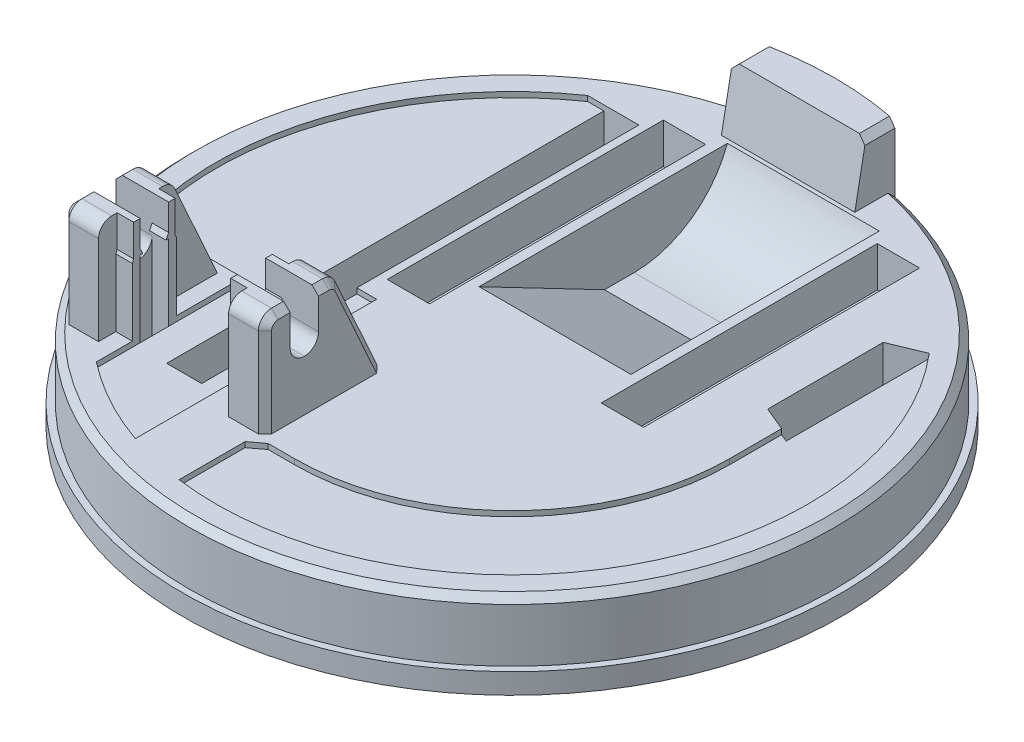
SolidWorks part; units mm, degrees
ref_plane "Front Plane" through (0, 0, 0) normal (0, 0, 1) x (1, 0, 0)
ref_plane "Top Plane" through (0, 0, 0) normal (0, 1, 0) x (1, 0, 0)
ref_plane "Right Plane" through (0, 0, 0) normal (1, 0, 0) x (0, 0, -1)
sketch "Sketch1" plane through (0, 0, 0) normal (0, 1, 0) x (1, 0, 0)
  circle A0 centre (0, 0) radius 49.9
  dimension "D1" = 99.8
extrude "Boss-Extrude1" add sketch "Sketch1" along normal blind 3.1
sketch "Sketch2" plane through (0, 0, 0) normal (0, -1, 0) x (1, 0, 0)
  circle A0 centre (0, 0) radius 48.9
  dimension "D1" = 97.8
extrude "Boss-Extrude2" add sketch "Sketch2" against normal blind 12.2
sketch "Sketch3" plane through (0, 12.2, 0) normal (0, 1, 0) x (1, 0, 0)
  line L0 (0, -48.9) -> (0, 41.8)
  line L2 (-10.1, 49.3) -> (10.1, 49.3)
  line L3 (-10.1, 49.3) -> (-10.1, 41.8)
  line L4 (-10.1, 41.8) -> (10.1, 41.8)
  line L5 (10.1, 49.3) -> (10.1, 41.8)
  circle A0 centre (0, 0) radius 48.9 construction
  circle A1 centre (0, 0) radius 48.9 construction
  point P12 (0, 41.8)
  circle M6 centre (0, 0) radius 48.9
  dimension "D1" = 90.7
  dimension "D2" = 7.5
  dimension "D3" = 20.2
extrude "Boss-Extrude3" add sketch "Sketch3" along normal blind 9 contours L5 L2 L3 L4 M6
sketch "Sketch4" plane through (10.1, 0, 0) normal (1, 0, 0) x (0, 0, -1)
  line L0 (41.8, 12.2) -> (43.5, 21.2)
  line L1 (47.8456, 21.2) -> (41.8, 21.2) construction
  line L2 (41.8, 21.2) -> (41.8, 12.2)
  line L3 (41.8, 21.2) -> (43.5, 21.2)
  dimension "D1" = 5.4
extrude "Cut-Extrude1" cut sketch "Sketch4" against normal up to surface (20.2 mm away) up to face at (-10.1, 16.7, -44.8228)
sketch "Sketch5" plane through (0, 12.2, 0) normal (0, 1, 0) x (1, 0, 0)
  line L0 (-10.1, 47.8456) -> (-10.1, 41.8) construction
  line L1 (-8.6, 41.2) -> (14.4, 41.2)
  line L2 (-8.6, 41.2) -> (-8.6, 3.6)
  line L3 (-8.6, 3.6) -> (14.4, 3.6)
  line L4 (14.4, 41.2) -> (14.4, 3.6)
  line L5 (-10.1, 41.8) -> (10.1, 41.8) construction
  dimension "D1" = 1.5
  dimension "D2" = 37.6
  dimension "D3" = 23
  dimension "D4" = 0.6
extrude "Cut-Extrude2" cut sketch "Sketch5" against normal blind 9.9
fillet "Fillet1" radius 15 1 edges at (2.9, 2.3, -41.2)
chamfer "Chamfer2" distance 9.9 distance2 19 1 edges at (2.9, 2.3, -3.6)
sketch "Sketch6" plane through (0, 12.2, 0) normal (0, 1, 0) x (1, 0, 0)
  line L0 (-8.6, 41.2) -> (-8.6, 3.6) construction
  line L1 (-16.5, 39.4) -> (-10.1, 39.4)
  line L2 (-16.5, 39.4) -> (-16.5, -2.4)
  line L3 (-16.5, -2.4) -> (-10.1, -2.4)
  line L4 (-10.1, 39.4) -> (-10.1, -2.4)
  line L5 (-8.6, 3.6) -> (14.4, 3.6) construction
  line L6 (-13.3, 35.1) -> (21.253, 35.1) construction
  line L7 (-16.5, 18.5) -> (-10.1, 18.5) construction
  line L8 (2.9, 41.2) -> (2.9, 3.6) construction
  line L9 (14.4, 41.2) -> (-8.6, 41.2) construction
  line L10 (22.3, -2.4) -> (15.9, -2.4)
  line L11 (15.9, 39.4) -> (15.9, -2.4)
  line L12 (22.3, 39.4) -> (15.9, 39.4)
  line L13 (22.3, 39.4) -> (22.3, -2.4)
  circle A0 centre (-13.3, 32.9) radius 2.2
  circle A1 centre (-13.3, 4.1) radius 2.2
  circle A2 centre (19.1, 4.1) radius 2.2
  circle A3 centre (19.1, 32.9) radius 2.2
  dimension "D6" = 4.4
  dimension "D1" = 1.5
  dimension "D2" = 41.8
  dimension "D3" = 6
  dimension "D4" = 6.4
  dimension "D5" = 3.2
  dimension "D7" = 4.3
extrude "Cut-Extrude3" cut sketch "Sketch6" against normal blind 6.1
sketch "Sketch7" plane through (0, 12.2, 0) normal (0, 1, 0) x (1, 0, 0)
  circle A0 centre (-13.3, 4.1) radius 2.2
  circle A1 centre (-13.3, 32.9) radius 2.2
  circle A2 centre (19.1, 32.9) radius 2.2
  circle A3 centre (19.1, 4.1) radius 2.2
  dimension "D1" = 4.4
  dimension "D2" = 4.4
  dimension "D3" = 4.4
  dimension "D4" = 4.4
extrude "Cut-Extrude4" cut sketch "Sketch7" against normal through all both and the other way through all
sketch "Sketch9" plane through (0, 12.2, 0) normal (0, 1, 0) x (1, 0, 0)
  line L0 (-16.5, 39.4) -> (-16.5, -2.4) construction
  line L1 (-23, 36.9) -> (-17.7, 36.9)
  line L2 (-23, 36.9) -> (-23, -29.3)
  line L3 (-23, -29.3) -> (-17.7, -29.3)
  line L4 (-17.7, 36.9) -> (-17.7, -29.3)
  line L5 (-10.1, 39.4) -> (-16.5, 39.4) construction
  dimension "D1" = 1.2
  dimension "D2" = 2.5
  dimension "D3" = 66.2
  dimension "D4" = 5.3
extrude "Cut-Extrude5" cut sketch "Sketch9" against normal through all both
sketch "Sketch12" plane through (0, 12.2, 0) normal (0, 1, 0) x (1, 0, 0)
  line L1 (-35.7, -14.4174) -> (-30.2, -14.4174)
  line L2 (-35.7, -14.4174) -> (-35.7, -32.4174)
  line L3 (-35.7, -32.4174) -> (-30.2, -32.4174)
  line L4 (-30.2, -14.4174) -> (-30.2, -32.4174)
  line L5 (-17.7, -29.3) -> (-17.7, 36.9) construction
  line L6 (-35.7, -32.4174) -> (-35.7, -33.4174)
  arc A2 (-10.1, 47.8456) -> (10.1, 47.8456) centre (0, 0) ccw construction
  dimension "D1" = 12.5
  dimension "D2" = 1
  dimension "D3" = 5.5
  dimension "D4" = 18
extrude "Boss-Extrude4" add sketch "Sketch12" along normal blind 15.5 contours L4 L1 L2 L3
sketch "Sketch13" plane through (-35.7, 0, 0) normal (-1, 0, 0) x (0, 0, 1)
  line L0 (14.4174, 12.2) -> (20.8859, 26.5232)
  line L1 (14.4174, 27.7) -> (32.4174, 27.7) construction
  line L2 (22.7086, 27.7) -> (30.4174, 27.7)
  line L3 (32.4174, 25.7) -> (32.4174, 12.2)
  line L4 (32.4174, 12.2) -> (14.4174, 12.2)
  line L5 (22.7086, 27.7) -> (14.4174, 27.7)
  line L6 (14.4174, 27.7) -> (14.4174, 12.2)
  line L7 (30.4174, 27.7) -> (32.4174, 27.7)
  line L8 (32.4174, 27.7) -> (32.4174, 25.7)
  arc A0 (30.4174, 27.7) -> (32.4174, 25.7) centre (30.4174, 25.7) cw
  arc A1 (20.8859, 26.5232) -> (22.7086, 27.7) centre (22.7086, 25.7) cw
  point P11 (32.4174, 27.7)
  point P14 (21.4174, 27.7)
  line M6 (32.4174, 12.2) -> (32.4174, 27.7)
  line M7 (32.4174, 27.7) -> (14.4174, 27.7)
  line M8 (14.4174, 27.7) -> (14.4174, 12.2)
  dimension "D2" = 2
  dimension "D1" = 11
extrude "Cut-Extrude6" cut sketch "Sketch13" against normal through all both and the other way through all contours L0 A1 M7 M8 | A0 M7 M6
sketch "Sketch14" plane through (0, 27.7, 0) normal (0, 1, 0) x (1, 0, 0)
  line L0 (-35.7, -24.3) -> (-30.2, -24.3)
  line L1 (-35.7, -22.7086) -> (-35.7, -30.4174) construction
  line L2 (-30.2, -22.7086) -> (-30.2, -30.4174) construction
  line L3 (-30.2, -24.3) -> (-30.2, -28.6)
  line L4 (-30.2, -14.4174) -> (-30.2, -32.4174) construction
  line L5 (-30.2, -28.6) -> (-35.7, -28.6)
  line L6 (-35.7, -14.4174) -> (-35.7, -32.4174) construction
  line L7 (-35.7, -28.6) -> (-35.7, -24.3)
  line L8 (-23, -29.3) -> (-17.7, -29.3) construction
  dimension "D1" = 0.7
  dimension "D2" = 4.3
extrude "Cut-Extrude7" cut sketch "Sketch14" against normal blind 7.8
fillet "Fillet2" radius 2.15 2 edges at (-32.95, 19.9, 24.3) (-32.95, 19.9, 28.6)
sketch "Sketch15" plane through (0, 12.2, 0) normal (0, 1, 0) x (1, 0, 0)
  line L0 (-20.35, -29.3) -> (-20.35, 36.9) construction
  line L1 (-23, -29.3) -> (-17.7, -29.3) construction
  line L2 (-17.7, 36.9) -> (-23, 36.9) construction
ref_plane "Plane2" through (-20.35, 0, 0) normal (1, 0, 0) x (0, 0, -1)
sketch "Sketch16" plane through (-30.2, 0, 0) normal (1, 0, 0) x (0, 0, -1)
  line L0 (-28.6, 27.7) -> (-28.6, 22.9)
  line L1 (-28.6, 22.05) -> (-28.6, 27.7) construction
  line L2 (-28.6, 22.9) -> (-29.6, 22.9)
  line L3 (-29.6, 22.9) -> (-29.6, 27.7)
  line L4 (-23.3, 22.9) -> (-23.1, 22.4)
  line L5 (-29.6, 27.7) -> (-28.6, 27.7)
  line L6 (-28.6, 27.7) -> (-30.4174, 27.7) construction
  line L7 (-28.6, 23.7) -> (-28.2, 22.9)
  line L8 (-28.2, 22.9) -> (-28.6, 22.9)
  line L9 (47.8456, 12.2) -> (-48.9, 12.2) construction
  line L10 (-28.6, 22.9) -> (-29.8, 22.9)
  line L11 (-28.6, 22.9) -> (-28.6, 12.2)
  line L12 (-28.6, 12.2) -> (-29.8, 12.2)
  line L13 (-29.8, 22.9) -> (-29.8, 12.2)
  line L14 (-29.6, 22.9) -> (-29.8, 22.4)
  line L16 (-26.45, 27.7) -> (-26.45, 23.5977) construction
  line L17 (-24.3, 12.2) -> (-23.1, 12.2)
  line L18 (-23.1, 22.9) -> (-23.1, 12.2)
  line L19 (-24.3, 22.9) -> (-23.1, 22.9)
  line L20 (-24.3, 22.9) -> (-24.3, 12.2)
  line L21 (-24.7, 22.9) -> (-24.3, 22.9)
  line L22 (-24.3, 23.7) -> (-24.7, 22.9)
  line L23 (-23.3, 22.9) -> (-23.3, 27.7)
  line L24 (-24.3, 22.9) -> (-23.3, 22.9)
  line L25 (-24.3, 27.7) -> (-24.3, 22.9)
  line L26 (-23.3, 27.7) -> (-24.3, 27.7)
  line M15 (-28.6, 22.05) -> (-28.6, 27.7)
  line M16 (-28.6, 27.7) -> (-30.4174, 27.7)
  line M19 (-32.4174, 12.2) -> (-14.4174, 12.2)
  line M22 (-22.7086, 27.7) -> (-24.3, 27.7)
  line M23 (-24.3, 27.7) -> (-24.3, 22.05)
  dimension "D1" = 1
  dimension "D2" = 4.8
  dimension "D3" = 0.4
  dimension "D4" = 0.8
  dimension "D5" = 1.2
  dimension "D6" = 0.5
  dimension "D7" = 2.15
extrude "Boss-Extrude5" add sketch "Sketch16" along normal blind 2.5 contours L3 L2 L0 M15 M16 | L8 L7 M15 | L2 L14 L13 L11 M19 M15 | L19 L23 M22 M23 | L22 L21 M23 | L20 L18 L4 L19 M23 M19
sketch "Sketch17" plane through (0, 12.2, 0) normal (0, 1, 0) x (1, 0, 0)
  line L1 (-27.7, -28.6) -> (-30.2, -28.6)
  line L2 (-27.7, -28.6) -> (-27.7, -24.3)
  line L3 (-27.7, -24.3) -> (-30.2, -24.3)
  line L4 (-30.2, -28.6) -> (-30.2, -24.3)
extrude "Cut-Extrude8" cut sketch "Sketch17" against normal through all contours L2 L3 L4 L1
mirror "Mirror2" about plane through (-20.35, 0, 0) normal (1, 0, 0) of "Boss-Extrude4", "Cut-Extrude6", "Cut-Extrude7", "Fillet2", "Boss-Extrude5", "Cut-Extrude8"
sketch "Sketch18" plane through (0, 12.2, 0) normal (0, 1, 0) x (1, 0, 0)
  line L0 (29.3, 26.9) -> (29.3, 9.4)
  line L1 (29.3, 9.4) -> (34.1, 7.4)
  line L2 (34.1, 7.4) -> (34.1, 28.9)
  line L3 (34.1, 28.9) -> (29.3, 26.9)
  line L4 (22.3, 39.4) -> (15.9, 39.4) construction
  line L5 (34.1, 18.15) -> (29.3, 18.15) construction
  line L6 (22.3, -2.4) -> (22.3, 39.4) construction
  dimension "D1" = 12.5
  dimension "D2" = 17.5
  dimension "D3" = 21.5
  dimension "D4" = 4.8
  dimension "D5" = 7
extrude "Cut-Extrude9" cut sketch "Sketch18" against normal through all
sketch "Sketch19" plane through (0, 12.2, 0) normal (0, 1, 0) x (1, 0, 0)
  line L0 (-6, -34.4174) -> (-6, -44.4174)
  line L1 (-5, -14.4174) -> (-5, -32.4174) construction
  line L2 (-6, -34.4174) -> (-4, -32.9174)
  line L3 (-5, -32.4174) -> (-10.5, -32.4174) construction
  line L4 (32.9174, 7.8928) -> (32.9174, 0)
  line L5 (-4, -32.9174) -> (8.2294, -32.9174) construction
  line L6 (29.3, 9.4) -> (34.1, 7.4) construction
  line L7 (-4, -32.9174) -> (0, -32.9174)
  line L8 (34.1, 28.9) -> (34.2177, 28.9491)
  line L9 (34.1, 28.9) -> (29.3, 26.9) construction
  line L10 (-17.7, -5.8) -> (-14.7, -5.8)
  line L11 (-17.7, -29.3) -> (-17.7, 36.9) construction
  line L12 (-14.7, -5.8) -> (-14.7, -42.3416)
  line L13 (-23, -29.3) -> (-17.7, -29.3) construction
  line L14 (-27.7, -29.8) -> (-27.7, -35.2365)
  line L15 (-27.7, -29.8) -> (-27.7, -23.1)
  line L16 (-27.7, -23.1) -> (-27.7, -13.1)
  line L17 (-27.7, -13.1) -> (-36.7, -13.1)
  line L18 (-36.7, -13.1) -> (-36.7, -25.7296)
  line L19 (-23, 36.9) -> (-25.4419, 36.9)
  circle A0 centre (0, 0) radius 44.8208
  circle A2 centre (0, 0) radius 32.9174
  point P2 (-6, -39.4174)
  line M7 (34.1, 28.9) -> (34.1, 7.4)
  line M8 (34.1, 7.4) -> (29.3, 9.4)
  line M28 (-27.7, -23.1) -> (-27.7, -24.3)
  line M29 (-27.7, -24.3) -> (-27.7, -28.6)
  line M30 (-27.7, -28.6) -> (-27.7, -29.8)
  line M36 (-17.7, 36.9) -> (-17.7, -29.3)
  line M37 (-17.7, -29.3) -> (-23, -29.3)
  line M38 (-23, -29.3) -> (-23, 36.9)
  dimension "D1" = 1
  dimension "D2" = 10
  dimension "D3" = 2
  dimension "D4" = 1.5
  dimension "D5" = 2
  dimension "D6" = 3
  dimension "D7" = 23.5
  dimension "D8" = 10
  dimension "D9" = 9
extrude "Cut-Extrude10" cut sketch "Sketch19" against normal blind 0.8 contours A2 L19 A0 L18 L17 M38 | A2 L17 L16 M38 | L14 L5 L12 A2 L16 M36 M37 M38 M28 M29 M30 | L5 L14 A0 L12 | A2 L12 L10 M36 | L5 L7 L2 L0 A0 | A2 L5 A0 L8 L4 M7 M8
sketch "Sketch21" plane through (0, 0, 0) normal (0, -1, 0) x (1, 0, 0)
  line L0 (0, 0) -> (0, -49.9) construction
  line L2 (3.6, -30.9) -> (-2.9, -30.9)
  line L3 (3.6, -30.9) -> (3.6, -20.5)
  line L4 (3.6, -20.5) -> (-2.9, -20.5)
  line L5 (-2.9, -30.9) -> (-2.9, -20.5)
  circle A0 centre (0, 0) radius 49.9 construction
  dimension "D1" = 2.9
  dimension "D2" = 3.6
  dimension "D3" = 10.4
  dimension "D4" = 20.5
extrude "Boss-Extrude6" add sketch "Sketch21" along normal blind 5.1
sketch "Sketch22" plane through (0, -5.1, 0) normal (0, -1, 0) x (1, 0, 0)
  line L0 (0.35, -20.5) -> (0.35, -30.9) construction
  line L1 (-1.8, -29.9) -> (2.5, -29.9)
  line L2 (-1.8, -29.9) -> (-1.8, -21.5)
  line L3 (-1.8, -21.5) -> (2.5, -21.5)
  line L4 (2.5, -29.9) -> (2.5, -21.5)
  line L5 (-1.8, -29.9) -> (2.5, -21.5) construction
  line L6 (-1.8, -21.5) -> (2.5, -29.9) construction
  line L7 (3.6, -20.5) -> (-2.9, -20.5) construction
  line L8 (-2.9, -30.9) -> (3.6, -30.9) construction
  line L9 (3.6, -25.7) -> (-2.9, -25.7) construction
  line L10 (3.6, -30.9) -> (3.6, -20.5) construction
  line L11 (-2.9, -20.5) -> (-2.9, -30.9) construction
  point P0 (0.35, -25.7)
  dimension "D1" = 8.4
  dimension "D2" = 4.3
extrude "Cut-Extrude11" cut sketch "Sketch22" against normal offset from surface (6.2 mm away) 1.2 up to face at (2.9, 2.3, -24.8468)
sketch "Sketch23" plane through (0, 0, 0) normal (0, -1, 0) x (1, 0, 0)
  line L0 (0, 0) -> (-6.7175, 6.7175) construction
  line L1 (0, 0) -> (14.1682, 0) construction
  circle A0 centre (-6.7175, 6.7175) radius 1.05
  circle A1 centre (6.7175, 6.7175) radius 1.05
  circle A2 centre (6.7175, -6.7175) radius 1.05
  circle A3 centre (-6.7175, -6.7175) radius 1.05
  circle A4 centre (-6.7175, 6.7175) radius 2.15
  circle A5 centre (-6.7175, -6.7175) radius 2.15
  circle A6 centre (6.7175, -6.7175) radius 2.15
  circle A7 centre (6.7175, 6.7175) radius 2.15
  point P15 (0, 0)
  dimension "D3" = 2.1
  dimension "D5" = 4.3
  dimension "D6" = 4.3
  dimension "D7" = 4.3
  dimension "D8" = 4.3
  dimension "D1" = 9.5
  dimension "D2" = 45
  dimension "D9" = 9.5
  dimension "D10" = 9.5
  dimension "D4" = 4
extrude "Boss-Extrude7" add sketch "Sketch23" along normal blind 1.2 and the other way offset from surface (1.2 mm away) 3 contours A4
sketch "Sketch24" plane through (0, 0, 0) normal (0, -1, 0) x (1, 0, 0)
  circle A0 centre (-6.7175, 6.7175) radius 1.05
  circle A1 centre (6.7175, 6.7175) radius 1.05
  circle A2 centre (6.7175, -6.7175) radius 1.05
  circle A3 centre (-6.7175, -6.7175) radius 1.05
  dimension "D1" = 2.1
  dimension "D2" = 2.1
  dimension "D3" = 2.1
  dimension "D4" = 2.1
extrude "Cut-Extrude12" cut sketch "Sketch24" against normal offset from surface (8 mm away) 4.2 up to face at (19.4071, 12.2, 10.2395)
chamfer "Chamfer3" distance 1 angle 45 1 edges at (0, 12.2, 48.9)
chamfer "Chamfer4" distance 1 angle 45 2 edges at (10.1, 21.2, -45.6728) (-10.1, 21.2, -45.6728)
chamfer "Chamfer5" distance 1 angle 45 6 edges at (-35.7, 18.7889, 32.4174) (-35.7, 27.1142, 31.8316) (-35.7, 27.7, 29.5087) (-35.7, 27.7, 23.5043) (-35.7, 27.3802, 21.6238) (-35.7, 19.3616, 17.6516)
chamfer "Chamfer6" distance 1 angle 45 5 edges at (-5, 19.3616, 17.6516) (-5, 27.3802, 21.6238) (-5, 27.7, 29.5087) (-5, 27.1142, 31.8316) (-5, 18.95, 32.4174)
sketch "Sketch25" plane through (0, 0, 0) normal (0, -1, 0) x (1, 0, 0)
  circle A0 centre (0, 0) radius 1.6236
extrude "Boss-Extrude8" add sketch "Sketch25" along normal blind 0.1 contours A0
